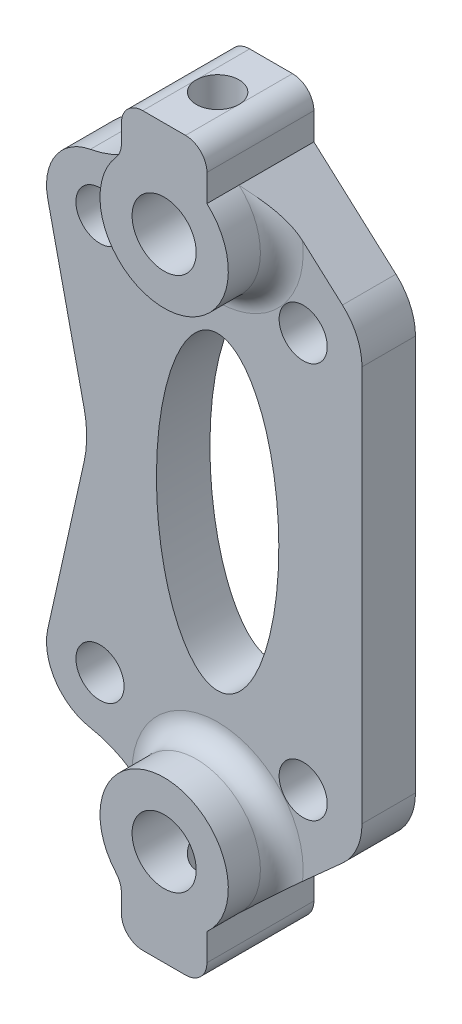
SolidWorks part; units mm, degrees
ref_plane "Front Plane" through (0, 0, 0) normal (0, 0, 1) x (1, 0, 0)
ref_plane "Top Plane" through (0, 0, 0) normal (0, 1, 0) x (1, 0, 0)
ref_plane "Right Plane" through (0, 0, 0) normal (1, 0, 0) x (0, 0, -1)
sketch "Sketch1" plane through (0, 0, 0) normal (0, 0, 1) x (1, 0, 0)
  line L0 (0, 0) -> (13.5, 0) construction
  line L10 (-4, -29.4721) -> (-4, -34)
  line L11 (-4, -34) -> (4, -34)
  line L16 (-15.8803, 17.4124) -> (-12.4847, 2.1751)
  line L17 (-15.8803, -17.4124) -> (-12.4847, -2.1751)
  line L37 (4, -34) -> (4, -29.4721)
  line L42 (0, -28) -> (0, -34) construction
  line L43 (4, 34) -> (4, 29.4721)
  line L44 (-4, 34) -> (4, 34)
  line L45 (4.005, 29.4677) -> (11.6712, 22.5954)
  line L46 (13.5, 18.5) -> (13.5, 0)
  line L47 (13.5, -18.5) -> (13.5, 0)
  line L48 (4.005, -29.4677) -> (11.6712, -22.5954)
  line L49 (-4, 29.4721) -> (-4, 34)
  circle A14 centre (0, 25) radius 3
  circle A15 centre (0, -25) radius 3
  circle A16 centre (0, 25) radius 6
  circle A17 centre (0, -25) radius 6
  arc A19 (-11.9023, 23.4179) -> (-15.8803, 17.4124) centre (-11, 18.5) ccw
  arc A20 (-5.14, 28.0952) -> (-11.9023, 23.4179) centre (-13.7068, 33.2538) cw
  arc A21 (-5.14, -28.0952) -> (-11.9023, -23.4179) centre (-13.7068, -33.2538) ccw
  arc A22 (-11.9023, -23.4179) -> (-15.8803, -17.4124) centre (-11, -18.5) cw
  arc A23 (-12.4847, 2.1751) -> (-12.4847, -2.1751) centre (-22.2453, 0) cw
  circle A24 centre (-11, 18.5) radius 2.25
  circle A25 centre (8, 18.5) radius 2.25
  circle A26 centre (-11, -18.5) radius 2.25
  circle A27 centre (8, -18.5) radius 2.25
  arc A28 (11.6712, 22.5954) -> (13.5, 18.5) centre (8, 18.5) cw
  arc A29 (11.6712, -22.5954) -> (13.5, -18.5) centre (8, -18.5) ccw
  ellipse E0 centre (0, 0) end of major axis (0, 14.4669) minor radius 5.7219
  point P31 (-12, 0)
  point P37 (4.005, -29.4677)
  point P42 (0, -34)
  dimension "D2" = 11
  dimension "D3" = 5
  dimension "D9" = 10
  dimension "D10" = 6
  dimension "D12" = 13.5
  dimension "D8" = 37
  dimension "D15" = 8
  dimension "D5" = 10
  dimension "D6" = 4.5
  dimension "D4" = 50
  dimension "D7" = 19
  dimension "D13" = 12
  dimension "D14" = 6
  dimension "D11" = 3
extrude "Boss-Extrude1" add sketch "Sketch1" along normal blind 5 contours A17 A16 | A16 | A16 A14 | A16 | A16 | A16 | A17 | A17 A15 | A17 | A17 | A17 region at (-4.4909, -28.7181, 0) region at (-7.6433, -24.4874, 0) region at (-4.4909, 28.7181, 0)
extrude "Boss-Extrude2" add sketch "Sketch1<8>" along normal blind 10 contours A17 A15 | A16 A14 | A17 L10 L11 L37 | A16 L43 L44 L49 region at (0, -32.2315, 0) region at (-4.4909, -28.7181, 0) region at (-4.4909, 28.7181, 0) region at (0, 32.2315, 0)
sketch "Sketch1<8>" plane through (0, 0, 0) normal (0, 0, 1) x (1, 0, 0) same geometry as "Sketch1"
fillet "Fillet1" radius 2 8 edges at (-4, -29.4721, 5) (-4, 29.4721, 5) (4, 34, 5) (-4, 34, 5) (4, -34, 5) (-4, -34, 5) (0.8905, 19.0665, 5) (0.8905, -19.0665, 5)
sketch "Sketch2" plane through (0, -34, 0) normal (0, -1, 0) x (1, 0, 0)
  line L0 (-2, 10) -> (-2, 0) construction
  line L1 (-2, 10) -> (-2, 0) construction
  circle A0 centre (0, 5) radius 2
  point P5 (-2, 5)
  dimension "D1" = 4
extrude "Cut-Extrude1" cut sketch "Sketch2" against normal up to next contours A0
extrude "Cut-Extrude2" cut sketch "Sketch2<3>" along normal up to next from surface starting at face at (0, 34, 5)
sketch "Sketch2<3>" plane through (0, -34, 0) normal (0, -1, 0) x (1, 0, 0) same geometry as "Sketch2"
equation "\"in_d\"=40"
equation "\"pipe_thick\"=2"
equation "\"rod_angle\"=20"
equation "\"rod_radius\"=33.5"
equation "\"rod_diameter\"=8"
equation "\"lin_bear_h\"=24"
equation "\"screw_radius\"=40"
equation "\"screw_angle\"=50"
equation "\"lin_bearing_d\"=15"
equation "\"drill_rod_pair\"=37"
equation "\"support_rod_w\"=50"
equation "\"vertical_slider_w\"=65"
equation "\"slope_angle\"=30"
